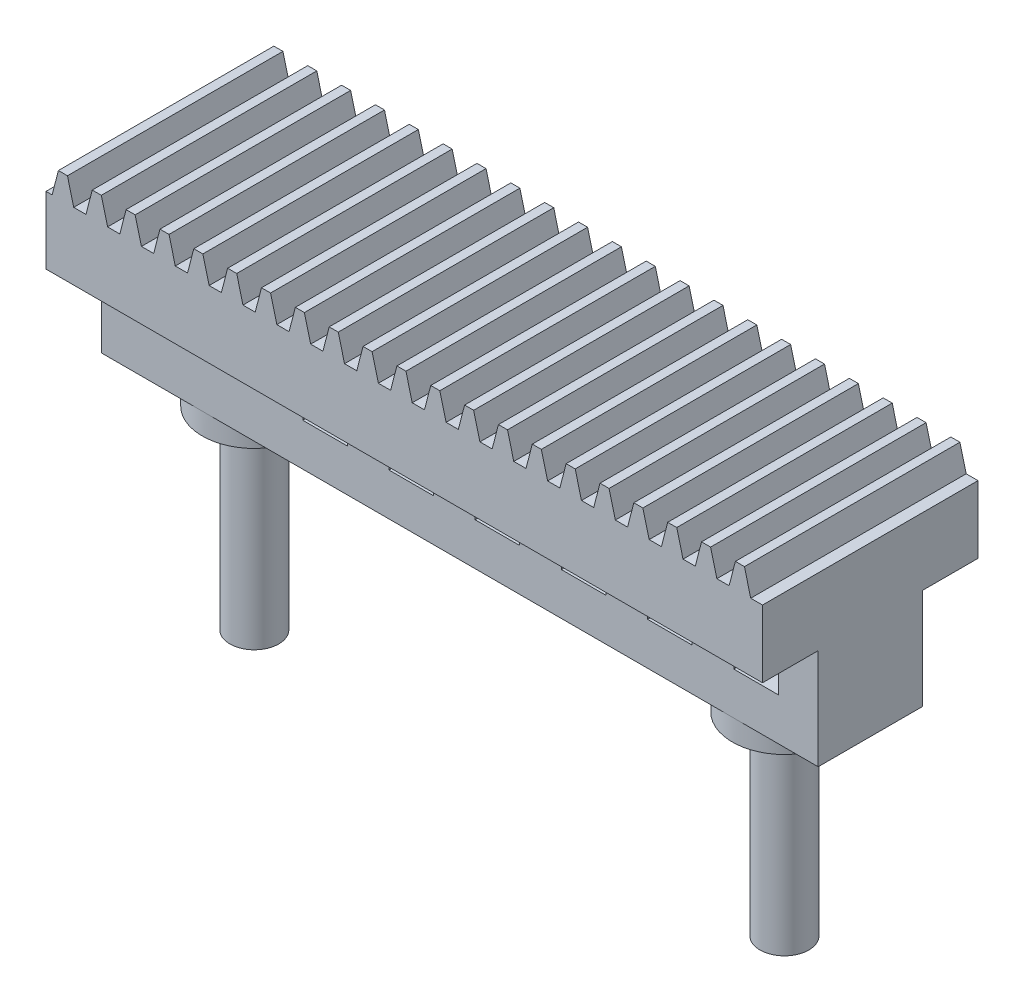
SolidWorks part; units mm, degrees
extrude "Blank" add sketch "BlankSke" against normal blind 20
sketch "BlankSke" plane through (0, 0, 0) normal (0, 0, 1) x (1, 0, 0)
  line L1 (0, 0) -> (100, 0)
  line L2 (0, 0) -> (0, 12.75)
  line L3 (0, 12.75) -> (100, 12.75)
  line L4 (100, 0) -> (100, 12.75)
  dimension "Length" = 100
ref_plane "Plane1" through (0, 0, 0) normal (0, 0, 1) x (1, 0, 0)
ref_plane "Plane2" through (0, 0, 0) normal (0, 1, 0) x (1, 0, 0)
ref_plane "Plane3" through (0, 0, 0) normal (1, 0, 0) x (0, 0, -1)
other "Configuration Table"
sketch "HoldingSke" plane through (0, 0, 0) normal (0, 1, 0) x (1, 0, 0)
  line L0 (0, 0) -> (0.0928, 0.6602)
  line L1 (-15, 0) -> (100, 0) construction
  line L2 (0, 0) -> (-2.1039, 2.3779)
  line L3 (0, 0) -> (-11.863, 4.5341)
  line L4 (0, 0) -> (7.9495, 3.3743)
  line L5 (0, 0) -> (-23.7986, -8.8762)
  line L6 (0, 0) -> (-10.5278, -7.1032)
  line L9 (-67.7845, 28.3722) -> (29.0302, 53.4102)
  line L10 (-76.2, 3.8779) -> (-64.95, 3.8779)
  line L11 (0, 0) -> (-20, 0)
  line L12 (-76.2, 101.6) -> (-76.147, 101.6)
  line L13 (24.9733, 27.94) -> (52.9518, 28.4284)
  line L14 (24.9733, 27.94) -> (24.9743, 27.94)
  line L15 (24.9733, 27.94) -> (100.4006, 29.5858)
  circle A0 centre (0, 0) radius 19.05
  circle A1 centre (0, 0) radius 5.625
  circle A2 centre (0, 0) radius 12.7
  dimension "Num_teeth" = 23
  dimension "Width" = 20
  dimension "Length" = 100
  dimension "Pitch_height" = 11.25
sketch "TooCutSkeIll" plane through (0, 0, 0) normal (0, 0, 1) x (1, 0, 0)
  line L0 (-1.7134, 12.705) -> (-0.9251, 9.6569)
  line L1 (-0.5611, 9.375) -> (0.5611, 9.375)
  line L2 (0.9251, 9.6569) -> (1.7134, 12.705)
  line L3 (100, 12.75) -> (0, 12.75) construction
  line L4 (0, 0) -> (0, 64.897) construction
  line L5 (-13.208, 11.25) -> (12.954, 11.25) construction
  line L6 (0, 0) -> (100, 0) construction
  line L7 (1.3371, 11.25) -> (1.3371, 48.7463) construction
  line L8 (-1.3371, 11.25) -> (-1.3371, 48.7463) construction
  line L9 (1.7715, 12.75) -> (1.7715, 12.7754)
  line L10 (-1.7715, 12.75) -> (-1.7715, 12.7754)
  line L11 (-1.7715, 12.7754) -> (1.7715, 12.7754)
  arc A0 (0.5611, 9.375) -> (0.9251, 9.6569) centre (0.5611, 9.751) ccw
  arc A1 (-0.9251, 9.6569) -> (-0.5611, 9.375) centre (-0.5611, 9.751) ccw
  arc A2 (1.7715, 12.75) -> (1.7134, 12.705) centre (1.7715, 12.69) ccw
  arc A3 (-1.7134, 12.705) -> (-1.7715, 12.75) centre (-1.7715, 12.69) ccw
  dimension "Addendum_plus" = 1.5254
  dimension "Pitch_height" = 11.25
  dimension "Pressure_angle" = 14.5
  dimension "Gap_width" = 2.6742
  dimension "Dedendum" = 1.875
extrude "ToothCutIll" [suppressed] cut sketch "TooCutSkeIll" against normal through all
sketch "TooCutSkeSim" plane through (0, 0, 0) normal (0, 0, 1) x (1, 0, 0)
  line L0 (0.8522, 9.375) -> (-0.8522, 9.375)
  line L1 (1.7316, 12.7754) -> (0.8522, 9.375)
  line L2 (0, 17.4625) -> (0, 53.467) construction
  line L3 (1.7316, 12.7754) -> (-1.7316, 12.7754)
  line L6 (-1.7316, 12.7754) -> (-0.8522, 9.375)
  line L9 (-1.3371, 11.25) -> (1.3371, 11.25) construction
  line L10 (0, 0) -> (100, 0) construction
  line L11 (1.3371, 11.25) -> (1.3371, 53.467) construction
  line L12 (-1.3371, 11.25) -> (-1.3371, 53.467) construction
  dimension "Addendum_plus" = 1.5254
  dimension "Pitch_height" = 11.25
  dimension "Pressure_angle" = 14.5
  dimension "Gap_width" = 2.6742
  dimension "Dedendum" = 1.875
extrude "ToothCutSim" cut sketch "TooCutSkeSim" against normal through all
pattern_linear "TeethCuts" count 23 spacing 4.7124 along (1, 0, 0) of "ToothCutIll", "ToothCutSim"
sketch "Croquis1" plane through (0, 0, 0) normal (0, 0, 1) x (1, 0, 0)
  line L89 (99.8124, 9.375) -> (98.108, 9.375)
  line L90 (98.108, 9.375) -> (97.2351, 12.75)
  line L91 (97.2351, 12.75) -> (95.9728, 12.75)
  line L92 (95.9728, 12.75) -> (95.1, 9.375)
  line L93 (95.1, 9.375) -> (93.3956, 9.375)
  line L94 (93.3956, 9.375) -> (92.5228, 12.75)
  line L95 (92.5228, 12.75) -> (91.2604, 12.75)
  line L96 (91.2604, 12.75) -> (90.3876, 9.375)
  line L97 (90.3876, 9.375) -> (88.6832, 9.375)
  line L98 (88.6832, 9.375) -> (87.8104, 12.75)
  line L99 (87.8104, 12.75) -> (86.548, 12.75)
  line L100 (86.548, 12.75) -> (85.6752, 9.375)
  line L101 (85.6752, 9.375) -> (83.9708, 9.375)
  line L102 (83.9708, 9.375) -> (83.098, 12.75)
  line L103 (83.098, 12.75) -> (81.8356, 12.75)
  line L104 (81.8356, 12.75) -> (80.9628, 9.375)
  line L105 (80.9628, 9.375) -> (79.2584, 9.375)
  line L106 (79.2584, 9.375) -> (78.3856, 12.75)
  line L107 (78.3856, 12.75) -> (77.1232, 12.75)
  line L108 (77.1232, 12.75) -> (76.2504, 9.375)
  line L109 (76.2504, 9.375) -> (74.546, 9.375)
  line L110 (74.546, 9.375) -> (73.6732, 12.75)
  line L111 (73.6732, 12.75) -> (72.4109, 12.75)
  line L112 (72.4109, 12.75) -> (71.538, 9.375)
  line L113 (71.538, 9.375) -> (69.8336, 9.375)
  line L114 (69.8336, 9.375) -> (68.9608, 12.75)
  line L115 (68.9608, 12.75) -> (67.6985, 12.75)
  line L116 (67.6985, 12.75) -> (66.8256, 9.375)
  line L117 (66.8256, 9.375) -> (65.1213, 9.375)
  line L118 (65.1213, 9.375) -> (64.2484, 12.75)
  line L119 (64.2484, 12.75) -> (62.9861, 12.75)
  line L120 (62.9861, 12.75) -> (62.1132, 9.375)
  line L121 (62.1132, 9.375) -> (60.4089, 9.375)
  line L122 (60.4089, 9.375) -> (59.536, 12.75)
  line L123 (59.536, 12.75) -> (58.2737, 12.75)
  line L124 (58.2737, 12.75) -> (57.4009, 9.375)
  line L125 (57.4009, 9.375) -> (55.6965, 9.375)
  line L126 (55.6965, 9.375) -> (54.8236, 12.75)
  line L127 (54.8236, 12.75) -> (53.5613, 12.75)
  line L128 (53.5613, 12.75) -> (52.6885, 9.375)
  line L129 (52.6885, 9.375) -> (50.9841, 9.375)
  line L130 (50.9841, 9.375) -> (50.1113, 12.75)
  line L131 (50.1113, 12.75) -> (48.8489, 12.75)
  line L132 (48.8489, 12.75) -> (47.9761, 9.375)
  line L133 (47.9761, 9.375) -> (46.2717, 9.375)
  line L134 (46.2717, 9.375) -> (45.3989, 12.75)
  line L135 (45.3989, 12.75) -> (44.1365, 12.75)
  line L136 (44.1365, 12.75) -> (43.2637, 9.375)
  line L137 (43.2637, 9.375) -> (41.5593, 9.375)
  line L138 (41.5593, 9.375) -> (40.6865, 12.75)
  line L139 (40.6865, 12.75) -> (39.4241, 12.75)
  line L140 (39.4241, 12.75) -> (38.5513, 9.375)
  line L141 (38.5513, 9.375) -> (36.8469, 9.375)
  line L142 (36.8469, 9.375) -> (35.9741, 12.75)
  line L143 (35.9741, 12.75) -> (34.7117, 12.75)
  line L144 (34.7117, 12.75) -> (33.8389, 9.375)
  line L145 (33.8389, 9.375) -> (32.1345, 9.375)
  line L146 (32.1345, 9.375) -> (31.2617, 12.75)
  line L147 (31.2617, 12.75) -> (29.9994, 12.75)
  line L148 (29.9994, 12.75) -> (29.1265, 9.375)
  line L149 (29.1265, 9.375) -> (27.4221, 9.375)
  line L150 (27.4221, 9.375) -> (26.5493, 12.75)
  line L151 (26.5493, 12.75) -> (25.287, 12.75)
  line L152 (25.287, 12.75) -> (24.4141, 9.375)
  line L153 (24.4141, 9.375) -> (22.7098, 9.375)
  line L154 (22.7098, 9.375) -> (21.8369, 12.75)
  line L155 (21.8369, 12.75) -> (20.5746, 12.75)
  line L156 (20.5746, 12.75) -> (19.7017, 9.375)
  line L157 (19.7017, 9.375) -> (17.9974, 9.375)
  line L158 (17.9974, 9.375) -> (17.1245, 12.75)
  line L159 (17.1245, 12.75) -> (15.8622, 12.75)
  line L160 (15.8622, 12.75) -> (14.9894, 9.375)
  line L161 (14.9894, 9.375) -> (13.285, 9.375)
  line L162 (13.285, 9.375) -> (12.4121, 12.75)
  line L163 (12.4121, 12.75) -> (11.1498, 12.75)
  line L164 (11.1498, 12.75) -> (10.277, 9.375)
  line L165 (10.277, 9.375) -> (8.5726, 9.375)
  line L166 (8.5726, 9.375) -> (7.6998, 12.75)
  line L167 (7.6998, 12.75) -> (6.4374, 12.75)
  line L168 (6.4374, 12.75) -> (5.5646, 9.375)
  line L169 (5.5646, 9.375) -> (3.8602, 9.375)
  line L170 (3.8602, 9.375) -> (2.9874, 12.75)
  line L171 (2.9874, 12.75) -> (1.725, 12.75)
  line L172 (1.725, 12.75) -> (0.8522, 9.375)
  line L173 (0.8522, 9.375) -> (0, 9.375)
  line L174 (0, 9.375) -> (0, 0)
  line L175 (0, 0) -> (100, 0)
  line L176 (100, 0) -> (100, 10.1006)
  line L177 (100, 10.1006) -> (99.8124, 9.375)
  line L178 (99.8124, 9.375) -> (98.108, 9.375)
  line L179 (98.108, 9.375) -> (97.2351, 12.75)
  line L180 (97.2351, 12.75) -> (95.9728, 12.75)
  line L181 (95.9728, 12.75) -> (95.1, 9.375)
  line L182 (95.1, 9.375) -> (93.3956, 9.375)
  line L183 (93.3956, 9.375) -> (92.5228, 12.75)
  line L184 (92.5228, 12.75) -> (91.2604, 12.75)
  line L185 (91.2604, 12.75) -> (90.3876, 9.375)
  line L186 (90.3876, 9.375) -> (88.6832, 9.375)
  line L187 (88.6832, 9.375) -> (87.8104, 12.75)
  line L188 (87.8104, 12.75) -> (86.548, 12.75)
  line L189 (86.548, 12.75) -> (85.6752, 9.375)
  line L190 (85.6752, 9.375) -> (83.9708, 9.375)
  line L191 (83.9708, 9.375) -> (83.098, 12.75)
  line L192 (83.098, 12.75) -> (81.8356, 12.75)
  line L193 (81.8356, 12.75) -> (80.9628, 9.375)
  line L194 (80.9628, 9.375) -> (79.2584, 9.375)
  line L195 (79.2584, 9.375) -> (78.3856, 12.75)
  line L196 (78.3856, 12.75) -> (77.1232, 12.75)
  line L197 (77.1232, 12.75) -> (76.2504, 9.375)
  line L198 (76.2504, 9.375) -> (74.546, 9.375)
  line L199 (74.546, 9.375) -> (73.6732, 12.75)
  line L200 (73.6732, 12.75) -> (72.4109, 12.75)
  line L201 (72.4109, 12.75) -> (71.538, 9.375)
  line L202 (71.538, 9.375) -> (69.8336, 9.375)
  line L203 (69.8336, 9.375) -> (68.9608, 12.75)
  line L204 (68.9608, 12.75) -> (67.6985, 12.75)
  line L205 (67.6985, 12.75) -> (66.8256, 9.375)
  line L206 (66.8256, 9.375) -> (65.1213, 9.375)
  line L207 (65.1213, 9.375) -> (64.2484, 12.75)
  line L208 (64.2484, 12.75) -> (62.9861, 12.75)
  line L209 (62.9861, 12.75) -> (62.1132, 9.375)
  line L210 (62.1132, 9.375) -> (60.4089, 9.375)
  line L211 (60.4089, 9.375) -> (59.536, 12.75)
  line L212 (59.536, 12.75) -> (58.2737, 12.75)
  line L213 (58.2737, 12.75) -> (57.4009, 9.375)
  line L214 (57.4009, 9.375) -> (55.6965, 9.375)
  line L215 (55.6965, 9.375) -> (54.8236, 12.75)
  line L216 (54.8236, 12.75) -> (53.5613, 12.75)
  line L217 (53.5613, 12.75) -> (52.6885, 9.375)
  line L218 (52.6885, 9.375) -> (50.9841, 9.375)
  line L219 (50.9841, 9.375) -> (50.1113, 12.75)
  line L220 (50.1113, 12.75) -> (48.8489, 12.75)
  line L221 (48.8489, 12.75) -> (47.9761, 9.375)
  line L222 (47.9761, 9.375) -> (46.2717, 9.375)
  line L223 (46.2717, 9.375) -> (45.3989, 12.75)
  line L224 (45.3989, 12.75) -> (44.1365, 12.75)
  line L225 (44.1365, 12.75) -> (43.2637, 9.375)
  line L226 (43.2637, 9.375) -> (41.5593, 9.375)
  line L227 (41.5593, 9.375) -> (40.6865, 12.75)
  line L228 (40.6865, 12.75) -> (39.4241, 12.75)
  line L229 (39.4241, 12.75) -> (38.5513, 9.375)
  line L230 (38.5513, 9.375) -> (36.8469, 9.375)
  line L231 (36.8469, 9.375) -> (35.9741, 12.75)
  line L232 (35.9741, 12.75) -> (34.7117, 12.75)
  line L233 (34.7117, 12.75) -> (33.8389, 9.375)
  line L234 (33.8389, 9.375) -> (32.1345, 9.375)
  line L235 (32.1345, 9.375) -> (31.2617, 12.75)
  line L236 (31.2617, 12.75) -> (29.9994, 12.75)
  line L237 (29.9994, 12.75) -> (29.1265, 9.375)
  line L238 (29.1265, 9.375) -> (27.4221, 9.375)
  line L239 (27.4221, 9.375) -> (26.5493, 12.75)
  line L240 (26.5493, 12.75) -> (25.287, 12.75)
  line L241 (25.287, 12.75) -> (24.4141, 9.375)
  line L242 (24.4141, 9.375) -> (22.7098, 9.375)
  line L243 (22.7098, 9.375) -> (21.8369, 12.75)
  line L244 (21.8369, 12.75) -> (20.5746, 12.75)
  line L245 (20.5746, 12.75) -> (19.7017, 9.375)
  line L246 (19.7017, 9.375) -> (17.9974, 9.375)
  line L247 (17.9974, 9.375) -> (17.1245, 12.75)
  line L248 (17.1245, 12.75) -> (15.8622, 12.75)
  line L249 (15.8622, 12.75) -> (14.9894, 9.375)
  line L250 (14.9894, 9.375) -> (13.285, 9.375)
  line L251 (13.285, 9.375) -> (12.4121, 12.75)
  line L252 (12.4121, 12.75) -> (11.1498, 12.75)
  line L253 (11.1498, 12.75) -> (10.277, 9.375)
  line L254 (10.277, 9.375) -> (8.5726, 9.375)
  line L255 (8.5726, 9.375) -> (7.6998, 12.75)
  line L256 (7.6998, 12.75) -> (6.4374, 12.75)
  line L257 (6.4374, 12.75) -> (5.5646, 9.375)
  line L258 (5.5646, 9.375) -> (3.8602, 9.375)
  line L259 (3.8602, 9.375) -> (2.9874, 12.75)
  line L260 (2.9874, 12.75) -> (1.725, 12.75)
  line L261 (1.725, 12.75) -> (0.8522, 9.375)
  line L262 (0.8522, 9.375) -> (0, 9.375)
  line L263 (0, 9.375) -> (0, 0)
  line L264 (0, 0) -> (100, 0)
  line L265 (100, 0) -> (100, 10.1006)
  line L266 (100, 10.1006) -> (99.8124, 9.375)
  dimension "D1" = 0
extrude "Saliente-Extruir1" add sketch "Croquis1" along normal blind 10
sketch "Croquis12" plane through (100, 0, 0) normal (1, 0, 0) x (0, 0, -1)
  line L4 (20, 10.1006) -> (-10, 10.1006)
  line L5 (-10, 10.1006) -> (-10, 0)
  line L6 (-10, 0) -> (20, 0)
  line L7 (20, 0) -> (20, 10.1006)
  line L8 (20, 10.1006) -> (-10, 10.1006)
  line L9 (-10, 10.1006) -> (-10, 0)
  line L10 (-10, 0) -> (20, 0)
  line L11 (20, 0) -> (20, 10.1006)
  dimension "D1" = 0
extrude "Cortar-Extruir1" cut sketch "Croquis12" against normal blind 0.25 and the other way through all
ref_plane "Plano1" through (0, 0, -5) normal (0, 0, 1) x (1, 0, 0)
sketch "Croquis13" plane through (0, 0, 0) normal (0, -1, 0) x (1, 0, 0)
  line L0 (0, -5) -> (107.4582, -5) construction
  line L1 (0, 2.25) -> (99.75, 2.25)
  line L2 (99.75, 10) -> (99.75, -20) construction
  line L3 (99.75, 2.25) -> (99.75, -12.25)
  line L4 (0, -20) -> (99.75, -20)
  line L5 (99.75, -20) -> (99.75, 10)
  line L6 (99.75, 10) -> (0, 10)
  line L7 (0, 10) -> (0, -20)
  line L11 (0, 10) -> (0, -20) construction
  line L12 (0, 2.25) -> (0, -12.25)
  line L13 (0, -12.25) -> (99.75, -12.25)
  point P11 (99.75, -5)
  dimension "D2" = 7.25
  dimension "D1" = 0
extrude "Saliente-Extruir6" add sketch "Croquis13" along normal blind 14
sketch "Croquis14" plane through (0, -14, 0) normal (0, -1, 0) x (1, 0, 0)
  line L0 (0, -5) -> (108.0787, -5) construction
  line L4 (0, 2.25) -> (0, -12.25)
  line L5 (0, -12.25) -> (99.75, -12.25)
  line L6 (99.75, -12.25) -> (99.75, 2.25)
  line L7 (99.75, 2.25) -> (0, 2.25)
  line L8 (0, 2.25) -> (0, -12.25) construction
  line L9 (0, -12.25) -> (99.75, -12.25) construction
  line L10 (99.75, -12.25) -> (99.75, 2.25) construction
  line L11 (99.75, 2.25) -> (0, 2.25) construction
  circle A0 centre (14, -5) radius 3.4
  circle A1 centre (87.8, -5) radius 3.4
  circle A2 centre (14, -5) radius 7.25
  circle A3 centre (87.8, -5) radius 7.25
  dimension "D2" = 6.8
  dimension "D3" = 73.8
  dimension "D4" = 14
  dimension "D1" = 0
extrude "Saliente-Extruir7" add sketch "Croquis14" along normal blind 3
sketch "Croquis15" plane through (0, -14, 0) normal (0, -1, 0) x (1, 0, 0)
  circle A0 centre (87.8, -5) radius 3.4 construction
  circle A1 centre (14, -5) radius 3.4 construction
  circle A2 centre (87.8, -5) radius 3.4
  circle A3 centre (14, -5) radius 3.4
extrude "Saliente-Extruir8" add sketch "Croquis15" along normal blind 30
sketch "Croquis16" plane through (0, 0, 2.25) normal (0, 0, 1) x (1, 0, 0)
  line L0 (0.926, -6.5) -> (118.1708, -6.5) construction
  line L1 (46.2, -8.1) -> (46.2, -4.9)
  line L2 (34.2, -8.1) -> (28, -8.1)
  line L3 (34.2, -8.1) -> (34.2, -4.9)
  line L4 (34.2, -4.9) -> (28, -4.9)
  line L5 (28, -8.1) -> (28, -4.9)
  line L6 (99.75, 0) -> (0, 0)
  line L7 (0, 0) -> (0, -14)
  line L8 (0, -14) -> (14, -14)
  line L9 (14, -14) -> (87.8, -14)
  line L10 (87.8, -14) -> (99.75, -14)
  line L11 (99.75, -14) -> (99.75, 0)
  line L12 (99.75, 0) -> (0, 0) construction
  line L13 (0, 0) -> (0, -14) construction
  line L14 (0, -14) -> (14, -14) construction
  line L15 (14, -14) -> (87.8, -14) construction
  line L16 (87.8, -14) -> (99.75, -14) construction
  line L17 (99.75, -14) -> (99.75, 0) construction
  line L18 (34.2, -8.1) -> (28, -4.9) construction
  line L19 (34.2, -4.9) -> (28, -8.1) construction
  line L20 (46.2, -4.9) -> (40, -4.9)
  line L21 (40, -8.1) -> (40, -4.9)
  line L22 (46.2, -8.1) -> (40, -8.1)
  line L23 (58.2, -8.1) -> (58.2, -4.9)
  line L24 (58.2, -4.9) -> (52, -4.9)
  line L25 (52, -8.1) -> (52, -4.9)
  line L26 (58.2, -8.1) -> (52, -8.1)
  line L27 (70.2, -8.1) -> (70.2, -4.9)
  line L28 (70.2, -4.9) -> (64, -4.9)
  line L29 (64, -8.1) -> (64, -4.9)
  line L30 (70.2, -8.1) -> (64, -8.1)
  line L31 (82.2, -8.1) -> (82.2, -4.9)
  line L32 (82.2, -4.9) -> (76, -4.9)
  line L33 (76, -8.1) -> (76, -4.9)
  line L34 (82.2, -8.1) -> (76, -8.1)
  line L35 (94.2, -8.1) -> (94.2, -4.9)
  line L36 (94.2, -4.9) -> (88, -4.9)
  line L37 (88, -8.1) -> (88, -4.9)
  line L38 (94.2, -8.1) -> (88, -8.1)
  point P6 (31.1, -6.5)
  dimension "D2" = 7.5
  dimension "D3" = 28
  dimension "D4" = 6.2
  dimension "D5" = 3.2
  dimension "D1" = 0
  dimension "D6" = 6
extrude "Cortar-Extruir2" cut sketch "Croquis16" against normal through all both and the other way through all
equation "' \"Module@HoldingSke\" = 6.35"
equation "' \"Num_teeth@HoldingSke\" = 12"
equation "' \"Ap@HoldingSke\" =  20"
equation "' \"Ap@HoldingSke\" = 20"
equation "' \"Width@HoldingSke\" = 0.25 * 25.4"
equation "' \"Show_teeth@HoldingSke\" = 500"
equation "' \"Backlash@HoldingSke\" = 0.009 * 25.4"
equation "' \"Addendum_fac@HoldingSke\" = 1.0"
equation "' \"Dedendum_fac@HoldingSke\" = 1.25"
equation "' \"Dedendum_add@HoldingSke\" = 0.00005 * 25.4"
equation "' \"Clearance_fac@HoldingSke\" = 0.25"
equation "' \"Pitch_height@HoldingSke\" = 1 * 25.4"
equation "' \"Length@HoldingSke\" = 4.71 * 25.4"
equation "\"Pitch@HoldingSke\" = 1 / \"Module@HoldingSke\""
equation "\"MPH@HoldingSke\" = \"Dedendum_fac@HoldingSke\" / \"Pitch@HoldingSke\" + 2 * \"Dedendum_add@HoldingSke\" + 0.002 * 25.4"
equation "\"MPH@HoldingSke\" = ((sgn( \"MPH@HoldingSke\" - \"Pitch_height@HoldingSke\")+1)*( \"MPH@HoldingSke\" - \"Pitch_height@HoldingSke\"))/2 + \"Pitch_height@HoldingSke\""
equation "\"Blank_height@BlankSke\" = \"Pitch_height@HoldingSke\" + \"Addendum_fac@HoldingSke\"  / \"Pitch@HoldingSke\" "
equation "\"Length@BlankSke\" =  \"Length@HoldingSke\""
equation "\"Face_width@Blank\" = \"Width@HoldingSke\""
equation "\"Pressure_angle@TooCutSkeIll\" = \"Ap@HoldingSke\""
equation "\"Addendum_plus@TooCutSkeIll\" =  \"Addendum_fac@HoldingSke\"  / \"Pitch@HoldingSke\" + 0.001 *25.4"
equation "\"Dedendum@TooCutSkeIll\" = \"Dedendum_fac@HoldingSke\"  / \"Pitch@HoldingSke\""
equation "\"Pitch_height@TooCutSkeIll\" =  \"MPH@HoldingSke\""
equation "\"Gap_width@TooCutSkeIll\" = 3.14159265 / 2 / \"Pitch@HoldingSke\" + 6 * \"Backlash@HoldingSke\""
equation "\"Pressure_angle@TooCutSkeSim\" = \"Ap@HoldingSke\""
equation "\"Addendum_plus@TooCutSkeSim\" =  \"Addendum_fac@HoldingSke\"  / \"Pitch@HoldingSke\" + 0.001 * 25.4"
equation "\"Dedendum@TooCutSkeSim\" = \"Dedendum_fac@HoldingSke\"  / \"Pitch@HoldingSke\""
equation "\"Pitch_height@TooCutSkeSim\" =  \"MPH@HoldingSke\""
equation "\"Gap_width@TooCutSkeSim\" = 3.14159265 / 2 / \"Pitch@HoldingSke\" + 6 * \"Backlash@HoldingSke\""
equation "\"Root_fillet@TooCutSkeIll\" = \"Clearance_fac@HoldingSke\" / \"Pitch@HoldingSke\" + \"Dedendum_add@HoldingSke\""
equation "\"Break_rad@TooCutSkeIll\" = 0.02 / \"Pitch@HoldingSke\" * 2"
equation "\"Linear_pitch@TeethCuts\" = 3.14159265 / \"Pitch@HoldingSke\""
equation "\"Num_teeth@HoldingSke\" = int( ( \"Length@HoldingSke\" + 0 ) / (3.14159265 / \"Pitch@HoldingSke\")) + 0.9999  + 1"
equation " \"Num_teeth@TeethCuts\" = int( \"Show_teeth@HoldingSke\" ) + 1"
equation " \"Num_teeth@TeethCuts\" = ((sgn( \"Num_teeth@TeethCuts\" - \"Num_teeth@HoldingSke\" )-1)*( \"Num_teeth@TeethCuts\" - \"Num_teeth@HoldingSke\" ))/-2+ \"Num_teeth@HoldingSke\""
equation " \"Num_teeth@TeethCuts\" = ((sgn( \"Num_teeth@TeethCuts\" - 2.0)+1)*( \"Num_teeth@TeethCuts\" - 2.0))/2 +2.0"
